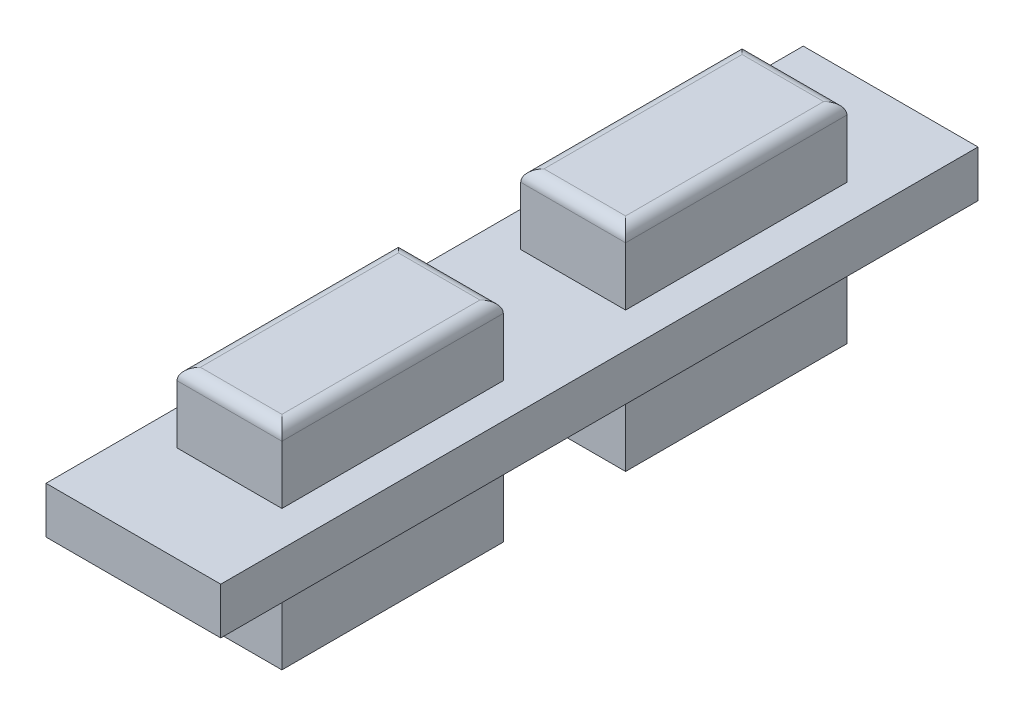
SolidWorks part; units mm, degrees
ref_plane "Front Plane" through (0, 0, 0) normal (0, 0, 1) x (1, 0, 0)
ref_plane "Top Plane" through (0, 0, 0) normal (0, 1, 0) x (1, 0, 0)
ref_plane "Right Plane" through (0, 0, 0) normal (1, 0, 0) x (0, 0, -1)
ref_plane "Plane1" through (0, 3.048, 0) normal (0, 1, 0) x (1, 0, 0)
sketch "Sketch1" plane through (0, 3.048, 0) normal (0, 1, 0) x (1, 0, 0)
  line L1 (-23.3428, -1.1236) -> (-19.5328, -1.1236)
  line L2 (-23.3428, -1.1236) -> (-23.3428, -17.6336)
  line L3 (-23.3428, -17.6336) -> (-19.5328, -17.6336)
  line L4 (-19.5328, -1.1236) -> (-19.5328, -17.6336)
  line L5 (-22.5808, -3.2191) -> (-20.2948, -3.2191)
  line L6 (-22.5808, -3.2191) -> (-22.5808, -8.0451)
  line L7 (-22.5808, -8.0451) -> (-20.2948, -8.0451)
  line L8 (-20.2948, -3.2191) -> (-20.2948, -8.0451)
  line L9 (-21.4378, -3.2191) -> (-21.4378, -15.5381) construction
  line L10 (-22.5808, -10.7121) -> (-20.2948, -10.7121)
  line L11 (-22.5808, -10.7121) -> (-22.5808, -15.5381)
  line L12 (-22.5808, -15.5381) -> (-20.2948, -15.5381)
  line L13 (-20.2948, -10.7121) -> (-20.2948, -15.5381)
  point P8 (-21.4378, -3.2191)
  point P9 (-21.4378, -1.1236)
  point P14 (-19.5328, -9.3786)
  point P17 (-21.4378, -9.3786)
  dimension "D1" = 3.81
  dimension "D2" = 2.286
  dimension "D3" = 4.826
  dimension "D4" = 4.826
  dimension "D5" = 2.667
  dimension "D6" = 16.51
extrude "Boss-Extrude1" add sketch "Sketch1" along normal blind 0.508 and the other way blind 0.508 contours L2 L3 L4 L1
extrude "Boss-Extrude2" add sketch "Sketch1<3>" along normal blind 2.032 and the other way blind 2.54 contours L13 L12 L11 L10 | L8 L7 L6 L5
sketch "Sketch1<3>" plane through (0, 3.048, 0) normal (0, 1, 0) x (1, 0, 0) same geometry as "Sketch1"
fillet "Fillet1" radius 0.254 8 edges at (-20.2948, 5.08, 5.6321) (-21.4378, 5.08, 8.0451) (-22.5808, 5.08, 5.6321) (-21.4378, 5.08, 3.2191) (-20.2948, 5.08, 13.1251) (-21.4378, 5.08, 15.5381) (-22.5808, 5.08, 13.1251) (-21.4378, 5.08, 10.7121)
